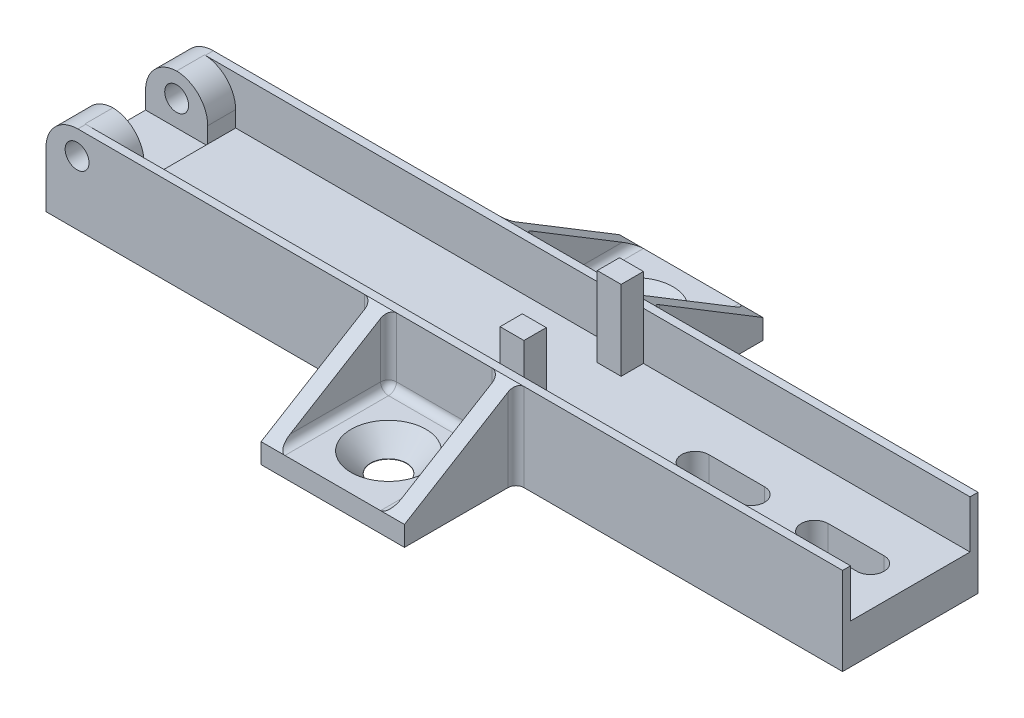
SolidWorks part; units mm, degrees
ref_plane "Ebene vorne" through (0, 0, 0) normal (0, 0, 1) x (1, 0, 0)
ref_plane "Ebene oben" through (0, 0, 0) normal (0, 1, 0) x (1, 0, 0)
ref_plane "Ebene rechts" through (0, 0, 0) normal (1, 0, 0) x (0, 0, -1)
sketch "Sketch1" plane through (0, 0, 0) normal (0, 1, 0) x (1, 0, 0)
  line L0 (-50, -7.5) -> (-50, 7.5)
  line L1 (-50, -7.5) -> (50, -7.5)
  line L2 (-50, 7.5) -> (50, 7.5)
  line L3 (50, -7.5) -> (50, 7.5)
  line L4 (-50, -7.5) -> (50, 7.5) construction
  line L5 (-50, 7.5) -> (50, -7.5) construction
  point P1 (0, 0)
  dimension "D1" = 15
  dimension "D2" = 100
extrude "Boss-Extrude1" add sketch "Sketch1" along normal blind 5
sketch "Sketch2" plane through (0, 5, 0) normal (0, 1, 0) x (1, 0, 0)
  line L0 (-50, -7.5) -> (50, -7.5) construction
  line L1 (-50, 7.5) -> (-42.1952, 7.5)
  line L2 (-50, 7.5) -> (-50, -7.5)
  line L3 (-50, -7.5) -> (-42.1952, -7.5)
  line L4 (-42.1952, 7.5) -> (-42.1952, -7.5)
extrude "Boss-Extrude2" add sketch "Sketch2" along normal blind 6
fillet "Fillet1" radius 4 1 edges at (-42.1952, 11, 0)
sketch "Sketch4" plane through (0, 11, 0) normal (0, 1, 0) x (1, 0, 0)
  line L0 (-42.1952, 0) -> (-50, 0) construction
  line L1 (-42.1952, -7.5) -> (-42.1952, 7.5) construction
  line L2 (-50, 7.5) -> (-50, -7.5) construction
  line L3 (-50, -4) -> (-42.1952, -4)
  line L4 (-50, -4) -> (-50, 4)
  line L5 (-42.1952, -4) -> (-42.1952, 4)
  line L6 (-50, 4) -> (-42.1952, 4)
  line L7 (-50, -4) -> (-42.1952, 4) construction
  line L8 (-42.1952, -4) -> (-50, 4) construction
  point P7 (-46.0976, 0)
  dimension "D1" = 8
extrude "Cut-Extrude2" cut sketch "Sketch4" against normal blind 6.2
sketch "Sketch5" plane through (0, 0, 0) normal (0, -1, 0) x (1, 0, 0)
  line L0 (45, 0) -> (38, 0) construction
  line L1 (45, -1.7) -> (38, -1.7)
  line L2 (45, 1.7) -> (38, 1.7)
  line L3 (30, 0) -> (23, 0) construction
  line L4 (30, -1.7) -> (23, -1.7)
  line L5 (30, 1.7) -> (23, 1.7)
  line L7 (50, 7.5) -> (50, -7.5) construction
  arc A0 (45, -1.7) -> (45, 1.7) centre (45, 0) ccw
  arc A1 (38, 1.7) -> (38, -1.7) centre (38, 0) ccw
  arc A2 (30, -1.7) -> (30, 1.7) centre (30, 0) ccw
  arc A3 (23, 1.7) -> (23, -1.7) centre (23, 0) ccw
  point P3 (41.5, 0)
  point P8 (26.5, 0)
  dimension "D2" = 15
  dimension "^3,4" = 3.4
  dimension "D3" = 3.4
  dimension "D4" = 5
  dimension "D5" = 7
  dimension "D6" = 7
extrude "Cut-Extrude3" cut sketch "Sketch5" against normal up to surface (5 mm away) up to face at (-11.4635, 5, 0)
sketch "Sketch6" plane through (0, 5, 0) normal (0, 1, 0) x (1, 0, 0)
  line L0 (-50, 4) -> (-50, -4) construction
  line L1 (-26, 7.5) -> (-26, -7.5) construction
  line L2 (50, 7.5) -> (-42.1952, 7.5) construction
  line L3 (-42.1952, -7.5) -> (50, -7.5) construction
  circle A0 centre (-26, 0) radius 2.5
  point P10 (-26, 0)
  dimension "D1" = 5
  dimension "D2" = 24
extrude "Boss-Extrude3" [suppressed] add sketch "Sketch6" along normal blind 15
sketch "Sketch7" plane through (0, 5, 0) normal (0, 1, 0) x (1, 0, 0)
  line L0 (-42.1952, -7.5) -> (50, -7.5) construction
  line L1 (6, -7.5) -> (9, -7.5)
  line L2 (6, -7.5) -> (6, -4.7)
  line L3 (6, -4.7) -> (9, -4.7)
  line L4 (9, -7.5) -> (9, -4.7)
  line L5 (0, 0) -> (16.5077, 0) construction
  line L6 (50, -7.5) -> (50, 7.5) construction
  line L7 (9, 7.5) -> (9, 4.7)
  line L8 (6, 4.7) -> (9, 4.7)
  line L9 (6, 7.5) -> (6, 4.7)
  line L10 (6, 7.5) -> (9, 7.5)
  dimension "D1" = 2.8
  dimension "D2" = 3
  dimension "D3" = 41
extrude "Boss-Extrude4" add sketch "Sketch7" along normal blind 10
sketch "Sketch8" plane through (0, 0, 7.5) normal (0, 0, 1) x (1, 0, 0)
  line L1 (50, 0) -> (-50, 0)
  line L2 (50, 0) -> (50, 11)
  line L3 (50, 11) -> (-50, 11)
  line L4 (-50, 0) -> (-50, 11)
extrude "Boss-Extrude5" add sketch "Sketch8" along normal blind 1
mirror "Mirror1" about plane through (0, 0, 0) normal (0, 0, 1) of "Boss-Extrude5"
sketch "Sketch3" plane through (0, 0, 8.5) normal (0, 0, 1) x (1, 0, 0)
  line L1 (-42.1952, 8) -> (-50, 8) construction
  line L2 (-42.1952, 11) -> (-42.1952, 5) construction
  line L3 (-50, 11) -> (-50, 0) construction
  circle A0 centre (-46.0976, 8) radius 1.5
  dimension "D1" = 3
extrude "Cut-Extrude1" cut sketch "Sketch3" against normal through all
fillet "Fillet2" radius 4 2 edges at (-50, 11, 6.25) (-50, 11, -6.25)
sketch "Sketch9" plane through (0, 0, 8.5) normal (0, 0, 1) x (1, 0, 0)
  line L0 (-50, 0) -> (50, 0) construction
  line L1 (-9, 0) -> (9, 0)
  line L2 (-9, 0) -> (-9, 2.5)
  line L3 (-9, 2.5) -> (9, 2.5)
  line L4 (9, 0) -> (9, 2.5)
  dimension "D1" = 2.5
  dimension "D2" = 18
extrude "Boss-Extrude6" add sketch "Sketch9" along normal blind 14
ref_plane "Plane1" through (0, 0, 0) normal (-1, 0, 0) x (0, 0, 1)
sketch "Sketch10" plane through (9, 0, 0) normal (1, 0, 0) x (0, 0, -1)
  line L0 (-8.5, 11) -> (-22.5, 2.5)
  line L1 (-22.5, 2.5) -> (-8.5, 2.5) construction
  line L2 (-22.5, 2.5) -> (-8.5, 2.5)
  line L3 (-8.5, 0) -> (-8.5, 11) construction
  line L4 (-8.5, 2.5) -> (-8.5, 11)
  point P5 (0, 0)
extrude "Boss-Extrude7" add sketch "Sketch10" against normal blind 2
mirror "Mirror2" about plane through (0, 0, 0) normal (-1, 0, 0) of "Boss-Extrude7"
hole_wizard "CSK for M4 Countersunk Flat Head Screw1" positions "Sketch13" profile "Sketch12" countersink size "M4" standard "DIN" end condition up to next
sketch "Sketch13" plane through (0, 2.5, 0) normal (0, 1, 0) x (1, 0, 0)
  line L0 (7, -15.5) -> (-7, -15.5) construction
  line L1 (7, -22.5) -> (7, -8.5) construction
  line L2 (-7, -22.5) -> (-7, -8.5) construction
  point P9 (0, -15.5)
sketch "Sketch12" plane through (0, 2.5, 15.5) normal (1, 0, 0) x (0, 0, 1)
  line L0 (0, 0) -> (0, 2.501)
  line L1 (0, 2.501) -> (2.25, 2.501)
  line L2 (2.25, 2.501) -> (2.25, 2.45)
  line L3 (2.25, 2.45) -> (4.7, 0)
  line L5 (4.7, 0) -> (0, 0)
  line L6 (-2.25, 2.45) -> (-4.7, 0) construction
  line L11 (0, -6.35) -> (0, 107.95) construction
  dimension "Thru Hole Dia." = 4.5
  dimension "Thru Hole Depth" = 2.501
  dimension "Near C'Sink Dia." = 9.4
  dimension "Near C'Sink Angle" = 90
mirror "Mirror5" about plane through (0, 0, 0) normal (0, 0, 1) of "CSK for M4 Countersunk Flat Head Screw1", "Mirror2", "Boss-Extrude7", "Boss-Extrude6"
fillet "Fillet4" radius 1 14 edges at (-7, 6.75, 8.5) (7, 6.75, 8.5) (9, 5.5, 8.5) (-9, 5.5, 8.5) (-7, 2.5, 15.5) (7, 2.5, 15.5) (0, 2.5, 8.5) (9, 5.5, -8.5) (-9, 5.5, -8.5) (7, 6.75, -8.5) (-7, 6.75, -8.5) (0, 2.5, -8.5) (-7, 2.5, -15.5) (7, 2.5, -15.5)
